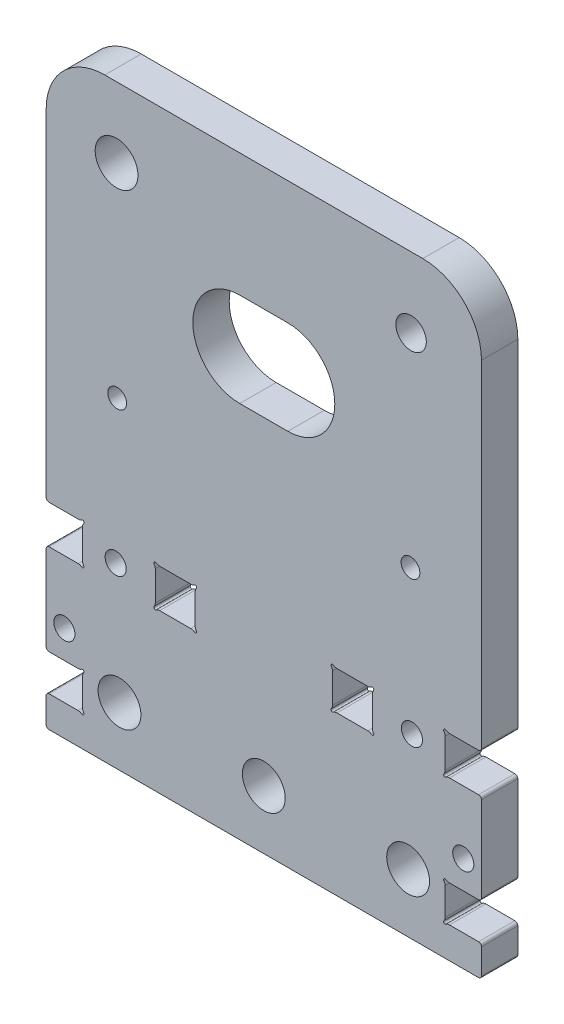
SolidWorks part; units mm, degrees
ref_plane "Front Plane" through (0, 0, 0) normal (0, 0, 1) x (1, 0, 0)
ref_plane "Top Plane" through (0, 0, 0) normal (0, 1, 0) x (1, 0, 0)
ref_plane "Right Plane" through (0, 0, 0) normal (1, 0, 0) x (0, 0, -1)
sketch "Sketch1" plane through (0, 0, 0) normal (0, 0, 1) x (1, 0, 0)
  line L0 (37.1, 0) -> (37.1, 59.3195) construction
  line L1 (0, 0) -> (74.2, 0)
  line L2 (0, 0) -> (0, 91.4)
  line L3 (10, 101.4) -> (64.2, 101.4)
  line L4 (74.2, 0) -> (74.2, 91.4)
  line L5 (0, 33.56) -> (74.2, 33.56) construction
  line L6 (-39.7056, 27) -> (34.4944, 27) construction
  line L7 (-40.5255, 5.3) -> (33.6745, 5.3) construction
  line L8 (-40.5255, 11.5) -> (33.6745, 11.5) construction
  line L9 (6.2, 79.4078) -> (6.2, -49920.5922) construction
  line L10 (68, 91.5017) -> (68, -49908.4983) construction
  line L11 (25.4, 75.1031) -> (25.4, -49924.8969) construction
  line L12 (18.6, 65.674) -> (18.6, -49934.326) construction
  line L13 (55.6, 36.7715) -> (55.6, -49963.2285) construction
  line L14 (48.8, 26.3174) -> (48.8, -49973.6826) construction
  line L16 (0, 33.56) -> (6.2, 33.56)
  line L17 (0, 33.56) -> (0, 27)
  line L18 (0, 27) -> (6.2, 27)
  line L19 (6.2, 33.56) -> (6.2, 27)
  line L20 (18.6, 33.56) -> (25.4, 33.56)
  line L21 (18.6, 33.56) -> (18.6, 27)
  line L22 (18.6, 27) -> (25.4, 27)
  line L23 (25.4, 33.56) -> (25.4, 27)
  line L24 (48.8, 33.56) -> (55.6, 33.56)
  line L25 (48.8, 33.56) -> (48.8, 27)
  line L26 (48.8, 27) -> (55.6, 27)
  line L27 (55.6, 33.56) -> (55.6, 27)
  line L28 (68, 33.56) -> (74.2, 33.56)
  line L29 (68, 33.56) -> (68, 27)
  line L30 (68, 27) -> (74.2, 27)
  line L31 (74.2, 33.56) -> (74.2, 27)
  line L32 (74.2, 5.3) -> (68, 5.3)
  line L33 (74.2, 5.3) -> (74.2, 11.5)
  line L34 (74.2, 11.5) -> (68, 11.5)
  line L35 (68, 5.3) -> (68, 11.5)
  line L36 (6.2, 11.5) -> (0, 11.5)
  line L37 (6.2, 11.5) -> (6.2, 5.3)
  line L38 (6.2, 5.3) -> (0, 5.3)
  line L39 (0, 11.5) -> (0, 5.3)
  arc A0 (64.2, 101.4) -> (74.2, 91.4) centre (64.2, 91.4) cw
  arc A1 (0, 91.4) -> (10, 101.4) centre (10, 91.4) cw
  circle A2 centre (12, 89.4) radius 3.65
  circle A3 centre (62.2, 89.4) radius 2.6
  circle A4 centre (37.1, 10) radius 3.65
  circle A5 centre (12.5, 10) radius 3.65
  circle A6 centre (61.7, 10) radius 3.65
  circle A7 centre (12.1, 54.75) radius 1.6
  circle A8 centre (62.1, 54.75) radius 1.6
  circle A9 centre (11.85, 30.28) radius 1.8
  circle A10 centre (3.1, 16.28) radius 1.8
  circle A11 centre (71.1, 16.28) radius 1.8
  circle A12 centre (62.35, 30.28) radius 1.8
  point P9 (0, 101.4)
  point P16 (37.1, 0)
  point P75 (6.2, 30.28)
  point P76 (3.1, 11.5)
  dimension "D3" = 10
  dimension "D8" = 7.3
  dimension "D9" = 5.2
  dimension "D11" = 6.2
  dimension "D12" = 6.2
  dimension "D14" = 3.2
  dimension "D27" = 3.6
  dimension "D1" = 74.2
  dimension "D2" = 101.4
  dimension "D4" = 12
  dimension "D5" = 12
  dimension "D6" = 12
  dimension "D7" = 12
  dimension "D10" = 10
  dimension "D13" = 49.2
  dimension "D15" = 50
  dimension "D16" = 54.75
  dimension "D17" = 6.8
  dimension "D18" = 6.8
  dimension "D19" = 12.4
  dimension "D20" = 12.4
  dimension "D21" = 5.3
  dimension "D22" = 6.2
  dimension "D23" = 15.5
  dimension "D24" = 6.56
  dimension "D25" = 16.28
  dimension "D26" = 50.5
extrude "Boss-Extrude1" add sketch "Sketch1" along normal blind 6.2 contours A1 L2 L16 L19 L18 L36 L37 L38 L1 L4 L32 L35 L34 L30 L29 L28 A0 L3 A11 A10 A9 A6 A5 A4 A3 A2 L20 L23 L22 L21 L24 L27 L26 L25 A7 region at (37.1741, 51.8984, 0)
sketch "Sketch2" plane through (0, 0, 6.2) normal (0, 0, 1) x (1, 0, 0)
  line L0 (33, 72.4) -> (41.2, 72.4) construction
  line L1 (33, 80.4) -> (41.2, 80.4)
  line L2 (33, 64.4) -> (41.2, 64.4)
  line L3 (74.2, 33.56) -> (74.2, 91.4) construction
  line L4 (0, 33.56) -> (0, 91.4) construction
  line L5 (10, 101.4) -> (64.2, 101.4) construction
  arc A0 (33, 80.4) -> (33, 64.4) centre (33, 72.4) ccw
  arc A1 (41.2, 64.4) -> (41.2, 80.4) centre (41.2, 72.4) ccw
  point P2 (37.1, 72.4)
  dimension "D1" = 8
  dimension "D2" = 33
  dimension "D3" = 33
  dimension "D4" = 29
extrude "Cut-Extrude1" cut sketch "Sketch2" against normal through all
sketch "Sketch3" plane through (0, 0, 6.2) normal (0, 0, 1) x (1, 0, 0)
  circle A0 centre (6.2, 33.56) radius 0.25
  circle A1 centre (6.2, 27) radius 0.25
  circle A2 centre (6.2, 11.5) radius 0.25
  circle A3 centre (6.2, 5.3) radius 0.25
  circle A4 centre (25.4, 27) radius 0.25
  circle A5 centre (18.6, 27) radius 0.25
  circle A6 centre (18.6, 33.56) radius 0.25
  circle A7 centre (25.4, 33.56) radius 0.25
  circle A8 centre (48.8, 33.56) radius 0.25
  circle A9 centre (48.8, 27) radius 0.25
  circle A10 centre (55.6, 33.56) radius 0.25
  circle A11 centre (55.6, 27) radius 0.25
  circle A12 centre (68, 33.56) radius 0.25
  circle A13 centre (68, 27) radius 0.25
  circle A14 centre (68, 11.5) radius 0.25
  circle A15 centre (68, 5.3) radius 0.25
  dimension "D1" = 0.5
extrude "Cut-Extrude2" cut sketch "Sketch3" against normal through all
fillet "Fillet1" radius 1 32 edges at (5.95, 11.5, 3.1) (6.2, 11.25, 3.1) (6.2, 5.55, 3.1) (5.95, 5.3, 3.1) (68, 5.55, 3.1) (68.25, 5.3, 3.1) (68, 11.25, 3.1) (68.25, 11.5, 3.1) (68.25, 33.56, 3.1) (68, 33.31, 3.1) (68, 27.25, 3.1) (68.25, 27, 3.1) (48.8, 27.25, 3.1) (48.8, 33.31, 3.1) (49.05, 33.56, 3.1) (55.35, 33.56, 3.1) (55.6, 33.31, 3.1) (55.6, 27.25, 3.1) (55.35, 27, 3.1) (49.05, 27, 3.1) (18.6, 27.25, 3.1) (18.85, 27, 3.1) (25.15, 27, 3.1) (25.4, 27.25, 3.1) (25.4, 33.31, 3.1) (25.15, 33.56, 3.1) (18.85, 33.56, 3.1) (18.6, 33.31, 3.1) (5.95, 33.56, 3.1) (6.2, 33.31, 3.1) (6.2, 27.25, 3.1) (5.95, 27, 3.1)
fillet "Fillet2" radius 0.5 10 edges at (0, 0, 3.1) (74.2, 0, 3.1) (74.2, 33.56, 3.1) (74.2, 27, 3.1) (74.2, 5.3, 3.1) (74.2, 11.5, 3.1) (0, 5.3, 3.1) (0, 11.5, 3.1) (0, 33.56, 3.1) (0, 27, 3.1)
